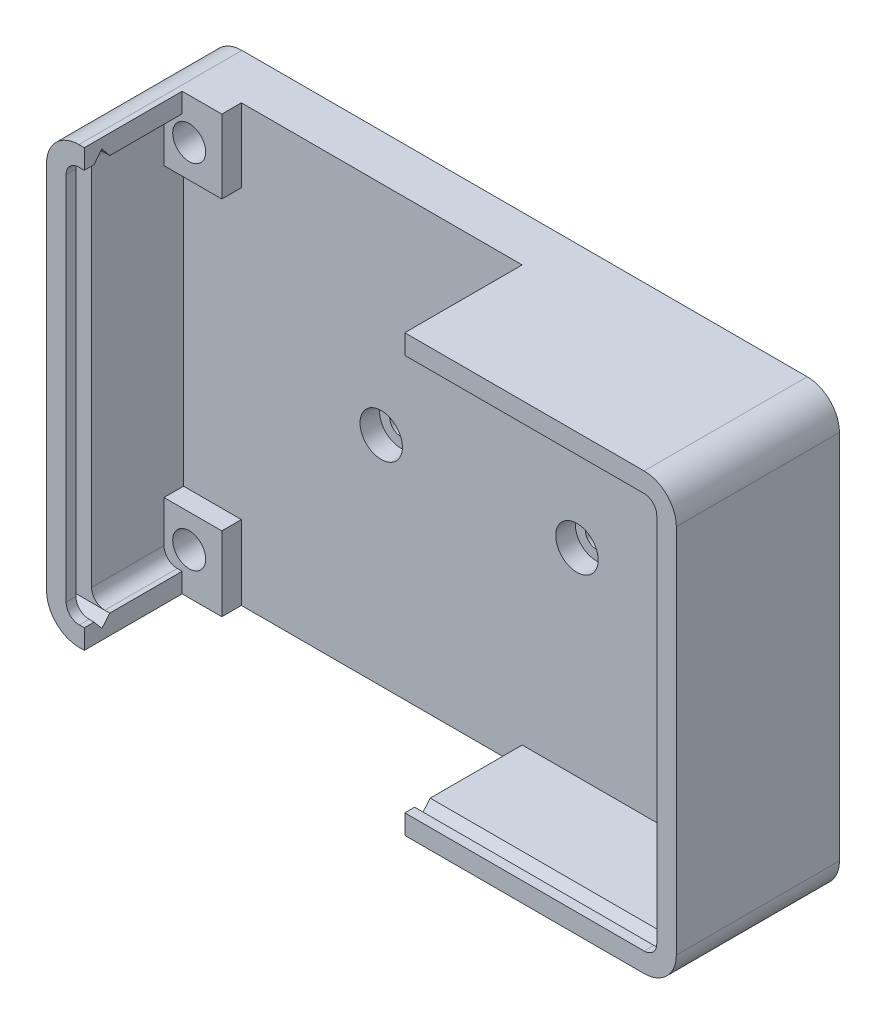
SolidWorks part; units mm, degrees
ref_plane "Front Plane" through (0, 0, 0) normal (0, 0, 1) x (1, 0, 0)
ref_plane "Top Plane" through (0, 0, 0) normal (0, 1, 0) x (1, 0, 0)
ref_plane "Right Plane" through (0, 0, 0) normal (1, 0, 0) x (0, 0, -1)
sketch "Sketch1" plane through (0, 0, -11.1517) normal (0, 0, -1) x (-1, 0, 0)
  line L0 (-25.223, 125.272) -> (-25.223, 68.523)
  line L1 (-22.223, 125.272) -> (-22.223, 68.523)
  line L2 (-113.733, 66.798) -> (-27.229, 66.798) construction
  line L26 (-27.174, 127.223) -> (-113.815, 127.223)
  line L28 (-27.174, 130.223) -> (-113.815, 130.223)
  line L29 (-118.748, 125.29) -> (-118.748, 68.431)
  line L30 (-113.815, 63.498) -> (-27.248, 63.498)
  line L39 (-115.748, 125.29) -> (-115.748, 68.431)
  line L40 (-113.815, 66.498) -> (-27.248, 66.498)
  line L42 (-22.223, 68.523) -> (-22.223, 125.272) construction
  line L43 (-25.223, 68.523) -> (-25.223, 125.272) construction
  arc A20 (-113.815, 127.223) -> (-115.748, 125.29) centre (-113.815, 125.29) ccw
  arc A21 (-113.815, 130.223) -> (-118.748, 125.29) centre (-113.815, 125.29) ccw
  arc A22 (-118.748, 68.431) -> (-113.815, 63.498) centre (-113.815, 68.431) ccw
  arc A23 (-27.248, 63.498) -> (-22.223, 68.523) centre (-27.248, 68.523) ccw
  arc A28 (-27.248, 66.498) -> (-25.223, 68.523) centre (-27.248, 68.523) ccw
  arc A29 (-25.223, 125.272) -> (-27.174, 127.223) centre (-27.174, 125.272) ccw
  arc A31 (-115.748, 68.431) -> (-113.815, 66.498) centre (-113.815, 68.431) ccw
  arc A32 (-22.223, 125.272) -> (-27.174, 130.223) centre (-27.174, 125.272) ccw
  dimension "D2" = 3
  dimension "D3" = 0.3
  dimension "D1" = 0.3
  dimension "D4" = 0.3
  dimension "D5" = 0.3
extrude "Boss-Extrude1" add sketch "Sketch1" against normal blind 7 contours L39 A31 L40 A28 A29 L26 A20 region at (70.4863, 96.8608, -11.1517)
extrude "Boss-Extrude2" add sketch "Sketch1<4>" against normal blind 25
sketch "Sketch1<4>" plane through (0, 0, -11.1517) normal (0, 0, -1) x (-1, 0, 0) same geometry as "Sketch1"
sketch "Sketch2" plane through (0, 0, -4.1517) normal (0, 0, 1) x (1, 0, 0)
  circle A0 centre (111.633, 123.952) radius 2.5265
  circle A1 centre (111.633, 69.901) radius 2.5265
  circle A2 centre (29.083, 69.901) radius 2.5265
  circle A3 centre (29.083, 123.952) radius 2.5265
  dimension "D1" = 5.053
extrude "Cut-Extrude1" cut sketch "Sketch2" against normal blind 6
sketch "Sketch3" plane through (0, 0, -4.1517) normal (0, 0, 1) x (1, 0, 0)
  line L0 (70.4945, 127.223) -> (70.5315, 66.498) construction
  line L1 (27.174, 127.223) -> (113.815, 127.223) construction
  line L2 (113.815, 66.498) -> (27.248, 66.498) construction
  point P1 (85.513, 96.8605)
  point P8 (70.513, 96.8605)
  point P9 (55.513, 96.8422)
  dimension "D1" = 15
hole_wizard "CBORE for M3 SHCS1" positions "Sketch3" profile "Sketch4" counterbore size "M3" standard "ANSI Metric"
sketch "Sketch4" plane through (55.513, 96.8422, -4.1517) normal (1, 0, 0) x (0, -1, 0)
  line L0 (0, 0) -> (0, 8.0215)
  line L1 (0, 8.0215) -> (1.7, 7)
  line L2 (1.7, 7) -> (1.7, 3)
  line L3 (1.7, 3) -> (3.25, 3)
  line L4 (3.25, 3) -> (3.25, 0)
  line L5 (3.25, 0) -> (0, 0)
  line L10 (0, 8.0215) -> (-1.7, 7) construction
  line L11 (0, -6.35) -> (0, 107.95) construction
  dimension "Hole Dia." = 3.4
  dimension "Hole Depth" = 7
  dimension "C'Bore Dia." = 6.5
  dimension "C'Bore Depth" = 3
  dimension "Drill Angle" = 118
ref_plane "Plane1" through (0, 96.8605, 0) normal (0, -1, 0) x (-1, 0, 0)
sketch "Sketch5" plane through (0, 96.8605, 0) normal (0, -1, 0) x (-1, 0, 0)
  line L0 (-113.815, -13.8483) -> (-27.248, -13.8483) construction
  line L1 (-77.123, -13.8483) -> (-28.005, -13.8483)
  line L2 (-77.123, -13.8483) -> (-77.123, 4.1517)
  line L3 (-77.123, 4.1517) -> (-28.005, 4.1517)
  line L4 (-28.005, -13.8483) -> (-28.005, 4.1517)
  line L5 (-33.005, -0.3) -> (-33.005, -7.4) construction
  line L6 (-72.123, -0.3) -> (-72.123, -7.4) construction
  line L8 (-113.815, 4.1517) -> (-27.248, 4.1517) construction
  dimension "D1" = 5
  dimension "D2" = 5
extrude "Cut-Extrude2" cut sketch "Sketch5" against normal through all both and the other way through all
sketch "Sketch6" plane through (22.223, -0.0074, 0) normal (-1, 0, 0) x (0, 0, 1)
  line L0 (13.8483, 68.5304) -> (13.8483, 125.2794) construction
  line L1 (9.9483, 128.7304) -> (12.3483, 128.7304)
  line L2 (9.9483, 128.7304) -> (9.9483, 65.0794)
  line L3 (9.9483, 65.0794) -> (12.3483, 65.0794)
  line L4 (12.3483, 128.7304) -> (12.3483, 65.0794)
  line L6 (13.8483, 130.2304) -> (-11.1517, 130.2304) construction
  line L7 (9.9483, 127.2304) -> (11.1483, 128.7304)
  line L8 (13.8483, 127.2304) -> (-4.1517, 127.2304) construction
  line L9 (11.1483, 128.7304) -> (12.3483, 127.2304)
  line L10 (12.3483, 66.5054) -> (11.1483, 65.0794)
  line L11 (13.8483, 66.5054) -> (-4.1517, 66.5054) construction
  line L12 (11.1483, 65.0794) -> (9.9483, 66.5054)
  point P4 (13.8483, 96.9049)
  point P7 (12.3483, 96.9049)
  dimension "D1" = 1.5
  dimension "D2" = 2.4
  dimension "D3" = 1.5
extrude "Cut-Extrude3" cut sketch "Sketch6" against normal offset from surface (95.025 mm away) 1.5 contours L4 L2 | L9 L7 L2 L4 | L12 L10 L4 L2 region at (22.223, 96.8791, 11.1483) up to face at (115.748, 96.8605, 4.8483) offset beyond the face yes
sketch "Sketch7" plane through (0, 0, -4.1517) normal (0, 0, 1) x (1, 0, 0)
  line L0 (22.223, 68.523) -> (22.223, 125.272) construction
  line L1 (28.005, 130.223) -> (77.123, 130.223) construction
  line L2 (27.174, 130.223) -> (28.005, 130.223) construction
  line L3 (22.223, 118.952) -> (22.223, 125.272)
  line L4 (28.005, 130.223) -> (34.083, 130.223)
  line L5 (27.174, 130.223) -> (28.005, 130.223)
  line L6 (34.083, 130.223) -> (34.083, 118.952)
  line L7 (34.083, 118.952) -> (22.223, 118.952)
  line L8 (118.748, 125.29) -> (118.748, 68.431) construction
  line L9 (77.123, 130.223) -> (113.815, 130.223) construction
  line L10 (118.748, 125.29) -> (118.748, 118.952)
  line L11 (106.633, 130.223) -> (113.815, 130.223)
  line L12 (113.815, 63.498) -> (77.123, 63.498) construction
  line L13 (113.815, 63.498) -> (106.633, 63.498)
  line L14 (28.005, 63.498) -> (77.123, 63.498) construction
  line L15 (28.005, 63.498) -> (27.248, 63.498) construction
  line L16 (22.223, 68.523) -> (22.223, 74.901)
  line L17 (28.005, 63.498) -> (34.083, 63.498)
  line L18 (28.005, 63.498) -> (27.248, 63.498)
  line L19 (34.083, 63.498) -> (34.083, 74.901)
  line L20 (34.083, 74.901) -> (22.223, 74.901)
  line L21 (106.633, 130.223) -> (106.633, 118.952)
  line L22 (106.633, 118.952) -> (118.748, 118.952)
  line L23 (118.748, 74.901) -> (106.633, 74.901)
  line L24 (106.633, 74.901) -> (106.633, 63.498)
  line L25 (118.748, 74.901) -> (118.748, 68.431)
  line L26 (22.223, 118.952) -> (22.223, 125.272)
  circle A0 centre (29.083, 123.952) radius 2.5265 construction
  circle A1 centre (29.083, 123.952) radius 2.5265
  arc A2 (27.174, 130.223) -> (22.223, 125.272) centre (27.174, 125.272) ccw construction
  arc A3 (27.174, 130.223) -> (22.223, 125.272) centre (27.174, 125.272) ccw
  circle A4 centre (111.633, 123.952) radius 2.5265 construction
  circle A5 centre (111.633, 123.952) radius 2.5265
  arc A6 (118.748, 125.29) -> (113.815, 130.223) centre (113.815, 125.29) ccw construction
  arc A7 (118.748, 125.29) -> (113.815, 130.223) centre (113.815, 125.29) ccw
  arc A8 (113.815, 63.498) -> (118.748, 68.431) centre (113.815, 68.431) ccw construction
  circle A9 centre (111.633, 69.901) radius 2.5265 construction
  arc A10 (113.815, 63.498) -> (118.748, 68.431) centre (113.815, 68.431) ccw
  circle A11 centre (111.633, 69.901) radius 2.5265
  arc A12 (22.223, 68.523) -> (27.248, 63.498) centre (27.248, 68.523) ccw construction
  arc A13 (22.223, 68.523) -> (27.248, 63.498) centre (27.248, 68.523) ccw
  circle A14 centre (29.083, 69.901) radius 2.5265 construction
  circle A15 centre (29.083, 69.901) radius 2.5265
  circle M9 centre (29.083, 69.901) radius 2.5265
  circle M10 centre (29.083, 123.952) radius 2.5265
  line M11 (27.248, 66.498) -> (28.005, 66.498)
  line M12 (28.005, 66.498) -> (28.005, 63.498)
  line M13 (28.005, 63.498) -> (77.123, 63.498)
  line M15 (77.123, 66.498) -> (113.815, 66.498)
  arc M16 (113.815, 66.498) -> (115.748, 68.431) centre (113.815, 68.431) ccw
  line M17 (115.748, 68.431) -> (115.748, 125.29)
  arc M18 (115.748, 125.29) -> (113.815, 127.223) centre (113.815, 125.29) ccw
  line M19 (113.815, 127.223) -> (77.123, 127.223)
  line M21 (77.123, 130.223) -> (28.005, 130.223)
  line M22 (28.005, 130.223) -> (28.005, 127.223)
  line M23 (28.005, 127.223) -> (27.174, 127.223)
  arc M24 (27.174, 127.223) -> (25.223, 125.272) centre (27.174, 125.272) ccw
  line M25 (25.223, 125.272) -> (25.223, 68.523)
  arc M26 (25.223, 68.523) -> (27.248, 66.498) centre (27.248, 68.523) ccw
  circle M28 centre (111.633, 123.952) radius 2.5265
  circle M29 centre (111.633, 69.901) radius 2.5265
  dimension "D1" = 5
  dimension "D2" = 5
  dimension "D3" = 5
  dimension "D4" = 5
  dimension "D5" = 5
  dimension "D6" = 5
  dimension "D7" = 5
extrude "Boss-Extrude3" add sketch "Sketch7" along normal up to surface (3 mm away) contours L7 L6 M21 M22 M23 M24 M25 M10 | L19 L20 M25 M26 M11 M12 M13 M9 | L21 L22 M17 M18 M19 M28 | L23 L24 M15 M16 M17 M29 region at (29.653, 74.7566, -4.1517) region at (25.3664, 122.112, -4.1517) region at (115.624, 71.666, -4.1517) region at (111.1905, 119.0751, -4.1517)
equation "\"D3@Sketch7\"=\"D1@Sketch7\""
equation "\"D4@Sketch7\"=\"D1@Sketch7\""
equation "\"D5@Sketch7\"=\"D1@Sketch7\""
equation "\"D6@Sketch7\"=\"D1@Sketch7\""
equation "\"D7@Sketch7\"=\"D1@Sketch7\""
